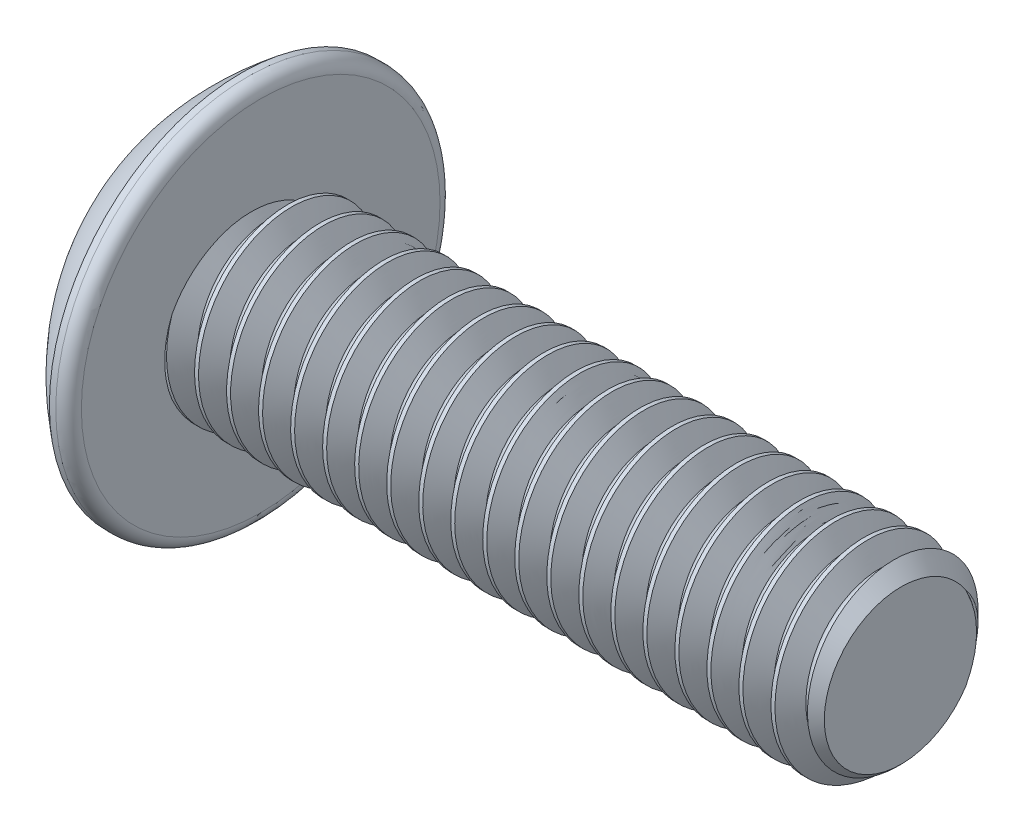
SolidWorks part; units mm, degrees
ref_plane "Ebene vorne" through (0, 0, 0) normal (0, 0, 1) x (1, 0, 0)
ref_plane "Ebene oben" through (0, 0, 0) normal (0, 1, 0) x (1, 0, 0)
ref_plane "Ebene rechts" through (0, 0, 0) normal (1, 0, 0) x (0, 0, -1)
sketch "Sketch1" plane through (0, 0, 0) normal (0, 0, 1) x (1, 0, 0)
  line L0 (-14.6254, 0) -> (0, 0) construction
  line L2 (2.7, 3) -> (2.8, 3)
  line L3 (3, 2.8) -> (3, 1.5)
  line L4 (3, 1.5) -> (13, 1.5)
  line L5 (13, 1.5) -> (13, 0)
  line L6 (1.13, 0) -> (13, 0)
  line L7 (3, 1.5) -> (3, 0)
  line L8 (1.13, 0) -> (16.6081, 0) construction
  arc A0 (3, 2.8) -> (2.8, 3) centre (2.8, 2.8) ccw
  spline S0 degree 2 poles (2.7, 3) (1.1958, 1.8272) (1.13, 0) knots 0 0 0 1 1 1
  point P8 (2.7, 3)
  point P16 (3, 3)
  dimension "D6" = 1.7
  dimension "D9" = 0.2
  dimension "D1" = 1.5
  dimension "D2" = 10
  dimension "D3" = 0.3
  dimension "D8" = 1.13
other "AlignGroup1"
other "AlignGroup2"
other "AlignGroup3"
revolve "Revolve1" add sketch "Sketch1" angle 360 about L0
sketch "Sketch3" plane through (3, 0, 0) normal (1, 0, 0) x (0, 0, -1)
  circle A0 centre (0, 0) radius 1.5
curve "Helix/Spiral1" pitch 0.5 height 11 radius 1.5 centre (3, 0, 0) axis (1, 0, 0) start towards (0, 0, -1)
sketch "Sketch4" plane through (0, 0, 0) normal (0, 1, 0) x (1, 0, 0)
  line L0 (-6.0413, 0) -> (11.0618, 0) construction
  line L1 (-6.0413, 1.5) -> (11.0618, 1.5) construction
  dimension "D1" = 1.5
chamfer "Chamfer1" distance 0.3 angle 45 1 edges at (13, 0, 1.5)
sketch "Sketch5" plane through (0, 0, 0) normal (0, 1, 0) x (1, 0, 0)
  line L0 (3.369, 1.3375) -> (2.3336, 1.3375) construction
  line L1 (-6.0413, 0) -> (11.0618, 0) construction
  line L2 (2.75, 1.6191) -> (2.75, 0.9933) construction
  line L3 (2.5, 1.5889) -> (2.5, 0.9756) construction
  line L4 (2.7812, 1.5) -> (2.9582, 1.1935)
  line L5 (2.7188, 1.5) -> (2.5418, 1.1935)
  line L6 (-6.0413, 1.5) -> (11.0618, 1.5) construction
  line L7 (3.6285, 1.1935) -> (3.4482, 1.1935) construction
  line L8 (3, 1.5889) -> (3, 0.9756) construction
  line L9 (2.7188, 1.5) -> (2.7812, 1.5)
  line L10 (2.5, 1.1774) -> (3, 1.1774)
  line L11 (2.75, 1.5541) -> (3, 1.1211) construction
  line L13 (2.75, 1.5541) -> (2.5, 1.1208) construction
  line L14 (3, -2.8) -> (3, 2.8) construction
  line L15 (3.2188, 1.5) -> (3.0418, 1.1935)
  line L16 (2.7812, 1.5) -> (3.2188, 1.5)
  arc A1 (2.9582, 1.1935) -> (3.0418, 1.1935) centre (3, 1.2395) ccw
  arc A2 (2.5418, 1.1935) -> (2.5, 1.1774) centre (2.5, 1.2395) cw
  spline S0 degree 3 poles (3, 1.5) (3.0104, 1.5) (3.0313, 1.4219) (3.0625, 1.0883) (3.1042, 0.4225) (3.1458, -0.4225) (3.1875, -1.0883) (3.2188, -1.4219) (3.25, -1.5391) (3.2813, -1.4219) (3.3125, -1.0883) (3.3542, -0.4225) (3.3958, 0.4225) (3.4375, 1.0883) (3.4688, 1.4219) (3.5, 1.5391) (3.5313, 1.4219) (3.5625, 1.0883) (3.6042, 0.4225) (3.6458, -0.4225) (3.6875, -1.0883) (3.7188, -1.4219) (3.75, -1.5391) (3.7812, -1.4219) (3.8125, -1.0883) (3.8542, -0.4225) (3.8958, 0.4225) (3.9375, 1.0883) (3.9688, 1.4219) (4, 1.5391) (4.0313, 1.4219) (4.0625, 1.0883) (4.1042, 0.4225) (4.1458, -0.4225) (4.1875, -1.0883) (4.2188, -1.4219) (4.25, -1.5391) (4.2813, -1.4219) (4.3125, -1.0883) (4.3542, -0.4225) (4.3958, 0.4225) (4.4375, 1.0883) (4.4688, 1.4219) (4.5, 1.5391) (4.5313, 1.4219) (4.5625, 1.0883) (4.6042, 0.4225) (4.6458, -0.4225) (4.6875, -1.0883) (4.7188, -1.4219) (4.75, -1.5391) (4.7813, -1.4219) (4.8125, -1.0883) (4.8542, -0.4225) (4.8958, 0.4225) (4.9375, 1.0883) (4.9688, 1.4219) (5, 1.5391) (5.0313, 1.4219) (5.0625, 1.0883) (5.1042, 0.4225) (5.1458, -0.4225) (5.1875, -1.0883) (5.2188, -1.4219) (5.25, -1.5391) (5.2813, -1.4219) (5.3125, -1.0883) (5.3542, -0.4225) (5.3958, 0.4225) (5.4375, 1.0883) (5.4688, 1.4219) (5.5, 1.5391) (5.5313, 1.4219) (5.5625, 1.0883) (5.6042, 0.4225) (5.6458, -0.4225) (5.6875, -1.0883) (5.7188, -1.4219) (5.75, -1.5391) (5.7813, -1.4219) (5.8125, -1.0883) (5.8542, -0.4225) (5.8958, 0.4225) (5.9375, 1.0883) (5.9688, 1.4219) (6, 1.5391) (6.0313, 1.4219) (6.0625, 1.0883) (6.1042, 0.4225) (6.1458, -0.4225) (6.1875, -1.0883) (6.2188, -1.4219) (6.25, -1.5391) (6.2812, -1.4219) (6.3125, -1.0883) (6.3542, -0.4225) (6.3958, 0.4225) (6.4375, 1.0883) (6.4688, 1.4219) (6.5, 1.5391) (6.5313, 1.4219) (6.5625, 1.0883) (6.6042, 0.4225) (6.6458, -0.4225) (6.6875, -1.0883) (6.7188, -1.4219) (6.75, -1.5391) (6.7813, -1.4219) (6.8125, -1.0883) (6.8542, -0.4225) (6.8958, 0.4225) (6.9375, 1.0883) (6.9688, 1.4219) (7, 1.5391) (7.0313, 1.4219) (7.0625, 1.0883) (7.1042, 0.4225) (7.1458, -0.4225) (7.1875, -1.0883) (7.2188, -1.4219) (7.25, -1.5391) (7.2813, -1.4219) (7.3125, -1.0883) (7.3542, -0.4225) (7.3958, 0.4225) (7.4375, 1.0883) (7.4688, 1.4219) (7.5, 1.5391) (7.5313, 1.4219) (7.5625, 1.0883) (7.6042, 0.4225) (7.6458, -0.4225) (7.6875, -1.0883) (7.7188, -1.4219) (7.75, -1.5391) (7.7813, -1.4219) (7.8125, -1.0883) (7.8542, -0.4225) (7.8958, 0.4225) (7.9375, 1.0883) (7.9688, 1.4219) (8, 1.5391) (8.0313, 1.4219) (8.0625, 1.0883) (8.1042, 0.4225) (8.1458, -0.4225) (8.1875, -1.0883) (8.2188, -1.4219) (8.25, -1.5391) (8.2813, -1.4219) (8.3125, -1.0883) (8.3542, -0.4225) (8.3958, 0.4225) (8.4375, 1.0883) (8.4688, 1.4219) (8.5, 1.5391) (8.5313, 1.4219) (8.5625, 1.0883) (8.6042, 0.4225) (8.6458, -0.4225) (8.6875, -1.0883) (8.7188, -1.4219) (8.75, -1.5391) (8.7813, -1.4219) (8.8125, -1.0883) (8.8542, -0.4225) (8.8958, 0.4225) (8.9375, 1.0883) (8.9688, 1.4219) (9, 1.5391) (9.0313, 1.4219) (9.0625, 1.0883) (9.1042, 0.4225) (9.1458, -0.4225) (9.1875, -1.0883) (9.2188, -1.4219) (9.25, -1.5391) (9.2813, -1.4219) (9.3125, -1.0883) (9.3542, -0.4225) (9.3958, 0.4225) (9.4375, 1.0883) (9.4688, 1.4219) (9.5, 1.5391) (9.5313, 1.4219) (9.5625, 1.0883) (9.6042, 0.4225) (9.6458, -0.4225) (9.6875, -1.0883) (9.7188, -1.4219) (9.75, -1.5391) (9.7813, -1.4219) (9.8125, -1.0883) (9.8542, -0.4225) (9.8958, 0.4225) (9.9375, 1.0883) (9.9688, 1.4219) (10, 1.5391) (10.0313, 1.4219) (10.0625, 1.0883) (10.1042, 0.4225) (10.1458, -0.4225) (10.1875, -1.0883) (10.2188, -1.4219) (10.25, -1.5391) (10.2813, -1.4219) (10.3125, -1.0883) (10.3542, -0.4225) (10.3958, 0.4225) (10.4375, 1.0883) (10.4688, 1.4219) (10.5, 1.5391) (10.5313, 1.4219) (10.5625, 1.0883) (10.6042, 0.4225) (10.6458, -0.4225) (10.6875, -1.0883) (10.7188, -1.4219) (10.75, -1.5391) (10.7813, -1.4219) (10.8125, -1.0883) (10.8542, -0.4225) (10.8958, 0.4225) (10.9375, 1.0883) (10.9688, 1.4219) (11, 1.5391) (11.0313, 1.4219) (11.0625, 1.0883) (11.1042, 0.4225) (11.1458, -0.4225) (11.1875, -1.0883) (11.2188, -1.4219) (11.25, -1.5391) (11.2813, -1.4219) (11.3125, -1.0883) (11.3542, -0.4225) (11.3958, 0.4225) (11.4375, 1.0883) (11.4688, 1.4219) (11.5, 1.5391) (11.5313, 1.4219) (11.5625, 1.0883) (11.6042, 0.4225) (11.6458, -0.4225) (11.6875, -1.0883) (11.7188, -1.4219) (11.75, -1.5391) (11.7813, -1.4219) (11.8125, -1.0883) (11.8542, -0.4225) (11.8958, 0.4225) (11.9375, 1.0883) (11.9688, 1.4219) (12, 1.5391) (12.0313, 1.4219) (12.0625, 1.0883) (12.1042, 0.4225) (12.1458, -0.4225) (12.1875, -1.0883) (12.2188, -1.4219) (12.25, -1.5391) (12.2813, -1.4219) (12.3125, -1.0883) (12.3542, -0.4225) (12.3958, 0.4225) (12.4375, 1.0883) (12.4688, 1.4219) (12.5, 1.5391) (12.5313, 1.4219) (12.5625, 1.0883) (12.6042, 0.4225) (12.6458, -0.4225) (12.6875, -1.0883) (12.7188, -1.4219) (12.75, -1.5391) (12.7813, -1.4219) (12.8125, -1.0883) (12.8542, -0.4225) (12.8958, 0.4225) (12.9375, 1.0883) (12.9688, 1.4219) (13, 1.5391) (13.0313, 1.4219) (13.0625, 1.0883) (13.1042, 0.4225) (13.1458, -0.4225) (13.1875, -1.0883) (13.2188, -1.4219) (13.25, -1.5391) (13.2813, -1.4219) (13.3125, -1.0883) (13.3542, -0.4225) (13.3958, 0.4225) (13.4375, 1.0883) (13.4687, 1.4219) (13.5, 1.5391) (13.5312, 1.4219) (13.5625, 1.0883) (13.6042, 0.4225) (13.6458, -0.4225) (13.6875, -1.0883) (13.7187, -1.4219) (13.75, -1.5391) (13.7812, -1.4219) (13.8125, -1.0883) (13.8542, -0.4225) (13.8958, 0.4225) (13.9375, 1.0883) (13.9687, 1.4219) (13.9896, 1.5) (14, 1.5) knots 0 0 0 0 0.002841 0.005682 0.008523 0.014205 0.017045 0.019886 0.022727 0.025568 0.028409 0.03125 0.036932 0.039773 0.042614 0.045455 0.048295 0.051136 0.053977 0.059659 0.0625 0.065341 0.068182 0.071023 0.073864 0.076705 0.082386 0.085227 0.088068 0.090909 0.09375 0.096591 0.099432 0.105114 0.107955 0.110795 0.113636 0.116477 0.119318 0.122159 0.127841 0.130682 0.133523 0.136364 0.139205 0.142045 0.144886 0.150568 0.153409 0.15625 0.159091 0.161932 0.164773 0.167614 0.173295 0.176136 0.178977 0.181818 0.184659 0.1875 0.190341 0.196023 0.198864 0.201705 0.204545 0.207386 0.210227 0.213068 0.21875 0.221591 0.224432 0.227273 0.230114 0.232955 0.235795 0.241477 0.244318 0.247159 0.25 0.252841 0.255682 0.258523 0.264205 0.267045 0.269886 0.272727 0.275568 0.278409 0.28125 0.286932 0.289773 0.292614 0.295455 0.298295 0.301136 0.303977 0.309659 0.3125 0.315341 0.318182 0.321023 0.323864 0.326705 0.332386 0.335227 0.338068 0.340909 0.34375 0.346591 0.349432 0.355114 0.357955 0.360795 0.363636 0.366477 0.369318 0.372159 0.377841 0.380682 0.383523 0.386364 0.389205 0.392045 0.394886 0.400568 0.403409 0.40625 0.409091 0.411932 0.414773 0.417614 0.423295 0.426136 0.428977 0.431818 0.434659 0.4375 0.440341 0.446023 0.448864 0.451705 0.454545 0.457386 0.460227 0.463068 0.46875 0.471591 0.474432 0.477273 0.480114 0.482955 0.485795 0.491477 0.494318 0.497159 0.5 0.502841 0.505682 0.508523 0.514205 0.517045 0.519886 0.522727 0.525568 0.528409 0.53125 0.536932 0.539773 0.542614 0.545455 0.548295 0.551136 0.553977 0.559659 0.5625 0.565341 0.568182 0.571023 0.573864 0.576705 0.582386 0.585227 0.588068 0.590909 0.59375 0.596591 0.599432 0.605114 0.607955 0.610795 0.613636 0.616477 0.619318 0.622159 0.627841 0.630682 0.633523 0.636364 0.639205 0.642045 0.644886 0.650568 0.653409 0.65625 0.659091 0.661932 0.664773 0.667614 0.673295 0.676136 0.678977 0.681818 0.684659 0.6875 0.690341 0.696023 0.698864 0.701705 0.704545 0.707386 0.710227 0.713068 0.71875 0.721591 0.724432 0.727273 0.730114 0.732955 0.735795 0.741477 0.744318 0.747159 0.75 0.752841 0.755682 0.758523 0.764205 0.767045 0.769886 0.772727 0.775568 0.778409 0.78125 0.786932 0.789773 0.792614 0.795455 0.798295 0.801136 0.803977 0.809659 0.8125 0.815341 0.818182 0.821023 0.823864 0.826705 0.832386 0.835227 0.838068 0.840909 0.84375 0.846591 0.849432 0.855114 0.857955 0.860795 0.863636 0.866477 0.869318 0.872159 0.877841 0.880682 0.883523 0.886364 0.889205 0.892045 0.894886 0.900568 0.903409 0.90625 0.909091 0.911932 0.914773 0.917614 0.923295 0.926136 0.928977 0.931818 0.934659 0.9375 0.940341 0.946023 0.948864 0.951705 0.954545 0.957386 0.960227 0.963068 0.96875 0.971591 0.974432 0.977273 0.980114 0.982955 0.985795 0.991477 0.994318 0.997159 1 1 1 1 construction
  dimension "D8" = 0
  dimension "D2" = 0.5
  dimension "D4" = 0.0541
  dimension "D6" = 0.0161
  dimension "D1" = 1.3375
  dimension "D3" = 60
  dimension "D5" = 0.25
  dimension "D7" = 1.1935
sweep "Cut-Sweep2" cut profiles "Sketch5" path "Helix/Spiral1" align with end faces yes
sketch "Sketch7" plane through (0, 0, 0) normal (1, 0, 0) x (0, 0, -1)
  line L1 (-1.1547, 0) -> (-0.5774, -1)
  line L2 (-0.5774, -1) -> (0.5774, -1)
  line L3 (0.5774, -1) -> (1.1547, 0)
  line L4 (1.1547, 0) -> (0.5774, 1)
  line L5 (0.5774, 1) -> (-0.5774, 1)
  line L6 (-0.5774, 1) -> (-1.1547, 0)
  circle A0 centre (0, 0) radius 1 construction
  dimension "D1" = 2
extrude "Cut-Extrude1" cut sketch "Sketch7" along normal blind 2.5
chamfer "Chamfer2" distance 0.1 angle 45 6 edges at (1.2906, -1, 0.139) (1.2906, -0.3796, 0.9355) (1.2906, 0.6204, 0.7965) (1.2906, 1, -0.139) (1.2906, 0.3796, -0.9355) (1.2906, -0.6204, -0.7965) first distance on face at (2.7, 0, 3)
